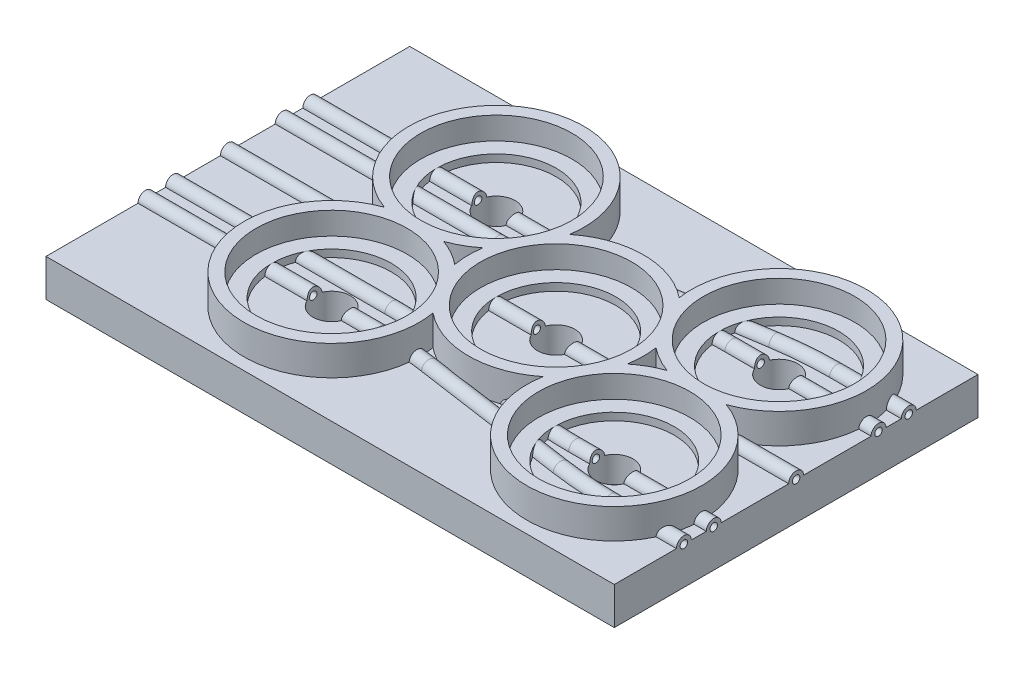
SolidWorks part; units mm, degrees
ref_plane "Front Plane" through (0, 0, 0) normal (0, 0, 1) x (1, 0, 0)
ref_plane "Top Plane" through (0, 0, 0) normal (0, 1, 0) x (1, 0, 0)
ref_plane "Right Plane" through (0, 0, 0) normal (1, 0, 0) x (0, 0, -1)
sketch "Sketch1" plane through (0, 0, 0) normal (0, 1, 0) x (1, 0, 0)
  line L1 (-42.9349, 26.7119) -> (33.1051, 26.7119)
  line L2 (-42.9349, 26.7119) -> (-42.9349, -21.9581)
  line L3 (-42.9349, -21.9581) -> (33.1051, -21.9581)
  line L4 (33.1051, 26.7119) -> (33.1051, -21.9581)
extrude "Boss-Extrude1" add sketch "Sketch1" along normal blind 5
sketch "Sketch2" plane through (0, 5, 0) normal (0, 1, 0) x (1, 0, 0)
  circle A0 centre (19.7951, 13.4019) radius 2.5
  circle A1 centre (19.7951, -8.6481) radius 2.5
  circle A2 centre (0.8851, 2.4819) radius 2.5
  circle A3 centre (-18.0249, 13.4019) radius 2.5
  circle A4 centre (-18.0249, -8.6481) radius 2.5
extrude "Cut-Extrude1" cut sketch "Sketch2" against normal blind 3.5
sketch "Sketch18" plane through (0, 5, 0) normal (0, 1, 0) x (1, 0, 0)
  circle A0 centre (0.8851, 2.4819) radius 2.5
  circle A1 centre (0.8851, 2.4819) radius 11.715
  circle A2 centre (-18.0249, 13.4019) radius 11.715
  circle A3 centre (-18.0249, 13.4019) radius 2.5
  circle A4 centre (19.7951, 13.4019) radius 2.5
  circle A5 centre (19.7951, 13.4019) radius 11.715
  circle A6 centre (19.7951, -8.6481) radius 2.5
  circle A7 centre (19.7951, -8.6481) radius 11.715
  circle A8 centre (-18.0249, -8.6481) radius 2.5
  circle A9 centre (-18.0249, -8.6481) radius 11.715
  circle A10 centre (0.8851, 2.4819) radius 8
  circle A11 centre (-18.0249, 13.4019) radius 8
  circle A12 centre (-18.0249, -8.6481) radius 8
  circle A13 centre (19.7951, -8.6481) radius 8
  circle A14 centre (19.7951, 13.4019) radius 8
extrude "Boss-Extrude6" add sketch "Sketch18" along normal blind 1 contours A9 A2 A1 A11 | A2 A9 | A1 A2 | A1 A9 A2 A12 | A1 A9 | A9 A1 A7 A5 A2 A10 | A1 A5 | A1 A7 | A7 A5 A1 A14 | A5 A7 | A5 A7 A1 A13 region at (12.2258, 5, -1.4944) region at (10.3401, 5, -7.9419) region at (11.3128, 5, -8.5036) region at (14.2083, 5, -1.2759) region at (10.3401, 5, 3.0831) region at (19.7951, 5, -2.3769) region at (-8.5699, 5, -7.9419) region at (-9.5426, 5, -8.5036) region at (-6.6794, 5, 7.6602) region at (-8.5699, 5, 3.0831) region at (-18.0249, 5, -2.3769)
sketch "Sketch21" plane through (0, 6, 0) normal (0, 1, 0) x (1, 0, 0)
  circle A0 centre (-18.0249, 13.4019) radius 11.715
  circle A1 centre (0.8851, 2.4819) radius 11.715
  circle A2 centre (19.7951, 13.4019) radius 11.715
  circle A3 centre (19.7951, -8.6481) radius 11.715
  circle A4 centre (-18.0249, -8.6481) radius 11.715
  circle A5 centre (-18.0249, 13.4019) radius 10.115
  circle A6 centre (0.8851, 2.4819) radius 10.115
  circle A7 centre (19.7951, -8.6481) radius 10.115
  circle A8 centre (-18.0249, -8.6481) radius 10.115
  circle A9 centre (19.7951, 13.4019) radius 10.115
  arc M3 (8.2564, -6.6234) -> (23.7562, 2.3769) centre (19.7951, -8.6481) ccw
  arc M4 (23.7562, 2.3769) -> (8.2165, 11.6192) centre (19.7951, 13.4019) ccw
  arc M5 (8.2165, 11.6192) -> (-6.4463, 11.6192) centre (0.8851, 2.4819) ccw
  arc M6 (-6.4463, 11.6192) -> (-21.9861, 2.3769) centre (-18.0249, 13.4019) ccw
  arc M8 (-6.4463, 11.6192) -> (-21.9861, 2.3769) centre (-18.0249, 13.4019) ccw
  arc M9 (-21.9861, 2.3769) -> (-6.4862, -6.6234) centre (-18.0249, -8.6481) ccw
  arc M11 (-21.9861, 2.3769) -> (-6.4862, -6.6234) centre (-18.0249, -8.6481) ccw
  arc M12 (-6.4862, -6.6234) -> (8.2564, -6.6234) centre (0.8851, 2.4819) ccw
  arc M13 (12.4637, 4.2645) -> (15.8339, 2.3769) centre (19.7951, 13.4019) ccw
  arc M14 (15.8339, 2.3769) -> (12.4238, 0.4571) centre (19.7951, -8.6481) ccw
  arc M15 (12.4238, 0.4571) -> (12.4637, 4.2645) centre (0.8851, 2.4819) ccw
  arc M17 (-10.6935, 4.2645) -> (-10.6536, 0.4571) centre (0.8851, 2.4819) ccw
  arc M18 (-10.6536, 0.4571) -> (-14.0638, 2.3769) centre (-18.0249, -8.6481) ccw
  arc M19 (-14.0638, 2.3769) -> (-10.6935, 4.2645) centre (-18.0249, 13.4019) ccw
extrude "Boss-Extrude7" add sketch "Sketch21" along normal blind 3 contours A4 A1 A5 M19 M6 M8 | A0 A4 | A1 A0 A8 M18 M9 M11 | A4 A3 A2 A0 A6 M12 M15 M5 M17 | A0 A1 | A1 A4 | A1 A2 | A1 A3 | A3 A1 A9 M4 M13 | A2 A1 A7 M14 M3 | A2 A3 region at (-6.6696, 6, -12.5328) region at (-18.0249, 6, -2.3769) region at (-18.0249, 6, -1.6542) region at (0.8851, 6, -13.8655) region at (-8.5699, 6, -7.9419) region at (18.9261, 6, -24.7571) region at (10.3401, 6, -7.9419) region at (-8.5699, 6, 3.0831) region at (10.3401, 6, 3.0831) region at (11.0093, 6, 3.477) region at (19.7951, 6, -2.3769)
sketch "Sketch26" plane through (-42.9349, 0, 0) normal (-1, 0, 0) x (0, 0, 1)
  line L0 (-26.7119, 5) -> (21.9581, 5) construction
  circle A0 centre (-2.3769, 5) radius 0.5
  circle A1 centre (-2.3769, 5) radius 1
sketch "Sketch27" plane through (0, 5, 0) normal (0, 1, 0) x (1, 0, 0)
  line L0 (-42.9349, 2.3769) -> (33.1051, 2.3769)
  line L1 (-42.9349, 3.3769) -> (-42.9349, 1.3769) construction
  line L2 (33.1051, -21.9581) -> (33.1051, 26.7119) construction
sweep "Sweep3" add profiles "Sketch26" path "Sketch27"
sketch "Sketch28" plane through (-42.9349, 0, 0) normal (-1, 0, 0) x (0, 0, 1)
  line L0 (-2.8769, 5) -> (-1.8769, 5) construction
  circle A0 centre (-2.3769, 5) radius 0.5
sweep "Cut-Sweep8" cut profiles "Sketch28" path "Sketch27<2>"
sketch "Sketch27<2>" plane through (0, 5, 0) normal (0, 1, 0) x (1, 0, 0) same geometry as "Sketch27"
sketch "Sketch31" plane through (-42.9349, 0, 0) normal (-1, 0, 0) x (0, 0, 1)
  line L1 (-1.3769, 5) -> (21.9581, 5) construction
  circle A0 centre (4.9581, 5) radius 0.5
  circle A1 centre (4.9581, 5) radius 1
sketch "Sketch32" plane through (0, 5, 0) normal (0, 1, 0) x (1, 0, 0)
  line L0 (-42.9349, -4.9581) -> (-13.6012, -4.9581)
  line L2 (-42.9349, -3.9581) -> (-42.9349, -5.9581) construction
  line L3 (-3.7115, -5.946) -> (4.7845, -7.6603)
  line L4 (14.6743, -8.6481) -> (33.1051, -8.6481)
  line L5 (33.1051, -21.9581) -> (33.1051, 1.3769) construction
  circle A0 centre (-18.0249, -8.6481) radius 10.115 construction
  circle A1 centre (19.7951, -8.6481) radius 10.115 construction
  circle A2 centre (19.7951, -8.6481) radius 10.115 construction
  arc A3 (4.7845, -7.6603) -> (14.6743, -8.6481) centre (14.6743, 41.3519) ccw
  arc A4 (-3.7115, -5.946) -> (-13.6012, -4.9581) centre (-13.6012, -54.9581) ccw
  point P17 (9.6801, -8.6481)
  point P20 (-8.607, -4.9581)
  dimension "D1" = 50
sweep "Sweep4" add profiles "Sketch31" path "Sketch32"
sketch "Sketch33" plane through (-42.9349, 0, 0) normal (-1, 0, 0) x (0, 0, 1)
  circle A0 centre (4.9581, 5) radius 0.5
sweep "Cut-Sweep9" cut profiles "Sketch33" path "Sketch32<2>"
sketch "Sketch32<2>" plane through (0, 5, 0) normal (0, 1, 0) x (1, 0, 0) same geometry as "Sketch32"
sketch "Sketch34" plane through (-42.9349, 0, 0) normal (-1, 0, 0) x (0, 0, 1)
  circle A0 centre (-9.7119, 5) radius 0.5
  circle A1 centre (-9.7119, 5) radius 1
sketch "Sketch36" plane through (0, 5, 0) normal (0, 1, 0) x (1, 0, 0)
  line L0 (-42.9349, 9.7119) -> (-14.0693, 9.7119)
  line L1 (-42.9349, 10.7119) -> (-42.9349, 8.7119) construction
  line L2 (-3.2736, 10.8912) -> (2.7467, 12.2225)
  line L3 (13.5423, 13.4019) -> (33.1051, 13.4019)
  line L4 (33.1051, 3.3769) -> (33.1051, 26.7119) construction
  circle A0 centre (-18.0249, 13.4019) radius 10.115 construction
  arc A1 (25.8565, 3.3769) -> (8.2165, 11.6192) centre (19.7951, 13.4019) ccw construction
  arc A2 (23.7562, 2.3769) -> (8.2165, 11.6192) centre (19.7951, 13.4019) ccw construction
  arc A3 (2.7467, 12.2225) -> (13.5423, 13.4019) centre (13.5423, -36.5981) cw
  arc A4 (-3.2736, 10.8912) -> (-14.0693, 9.7119) centre (-14.0693, 59.7119) cw
  point P19 (8.0801, 13.4019)
  point P22 (-8.607, 9.7119)
  dimension "D1" = 50
sweep "Sweep5" add profiles "Sketch34" path "Sketch36"
sketch "Sketch37" plane through (-42.9349, 0, 0) normal (-1, 0, 0) x (0, 0, 1)
  line L0 (-10.2119, 5) -> (-9.2119, 5) construction
  circle A0 centre (-9.7119, 5) radius 0.5
sweep "Cut-Sweep10" cut profiles "Sketch37" path "Sketch36<2>"
sketch "Sketch36<2>" plane through (0, 5, 0) normal (0, 1, 0) x (1, 0, 0) same geometry as "Sketch36"
sketch "Sketch38" plane through (-42.9349, 0, 0) normal (-1, 0, 0) x (0, 0, 1)
  line L1 (5.9581, 5) -> (21.9581, 5) construction
  circle A0 centre (8.6481, 5) radius 0.5
  circle A1 centre (8.6481, 5) radius 1
sketch "Sketch39" plane through (0, 5, 0) normal (0, 1, 0) x (1, 0, 0)
  line L0 (-42.9349, -8.6481) -> (-11.5008, -8.6481)
  line L1 (-42.9349, -7.6481) -> (-42.9349, -9.6481) construction
  line L3 (-4.3559, -9.1613) -> (16.2411, -12.135)
  line L4 (23.3859, -12.6481) -> (33.1051, -12.6481)
  line L5 (33.1051, -21.9581) -> (33.1051, -9.6481) construction
  circle A0 centre (-18.0249, -8.6481) radius 10.115 construction
  arc A2 (16.2411, -12.135) -> (23.3859, -12.6481) centre (23.3859, 37.3519) ccw
  arc A3 (-4.3559, -9.1613) -> (-11.5008, -8.6481) centre (-11.5008, -58.6481) ccw
  point P13 (-7.9099, -8.6481)
  dimension "D1" = 50
sweep "Sweep6" add profiles "Sketch38" path "Sketch39"
sketch "Sketch40" plane through (-42.9349, 0, 0) normal (-1, 0, 0) x (0, 0, 1)
  line L0 (8.1481, 5) -> (9.1481, 5) construction
  circle A0 centre (8.6481, 5) radius 0.5
sweep "Cut-Sweep11" cut profiles "Sketch40" path "Sketch39<2>"
sketch "Sketch39<2>" plane through (0, 5, 0) normal (0, 1, 0) x (1, 0, 0) same geometry as "Sketch39"
sketch "Sketch41" plane through (-42.9349, 0, 0) normal (-1, 0, 0) x (0, 0, 1)
  line L1 (-26.7119, 5) -> (-10.7119, 5) construction
  circle A0 centre (-13.4019, 5) radius 0.5
  circle A1 centre (-13.4019, 5) radius 1
sketch "Sketch42" plane through (0, 5, 0) normal (0, 1, 0) x (1, 0, 0)
  line L0 (-42.9349, 13.4019) -> (-10.1825, 13.4019)
  line L1 (-42.9349, 13.9019) -> (-42.9349, 12.9019) construction
  line L3 (-2.4835, 13.9982) -> (15.8008, 16.8476)
  line L4 (23.4998, 17.4439) -> (33.1051, 17.4439)
  line L5 (33.1051, 14.4019) -> (33.1051, 26.7119) construction
  arc A0 (-6.4463, 11.6192) -> (-21.9861, 2.3769) centre (-18.0249, 13.4019) ccw construction
  arc A1 (15.8008, 16.8476) -> (23.4998, 17.4439) centre (23.4998, -32.5561) cw
  arc A2 (-2.4835, 13.9982) -> (-10.1825, 13.4019) centre (-10.1825, 63.4019) cw
  point P10 (0, 0)
  point P17 (-6.3099, 13.4019)
  dimension "D1" = 50
sweep "Sweep7" add profiles "Sketch41" path "Sketch42"
sketch "Sketch43" plane through (-42.9349, 0, 0) normal (-1, 0, 0) x (0, 0, 1)
  line L0 (-12.9019, 5) -> (-13.9019, 5) construction
  circle A0 centre (-13.4019, 5) radius 0.5
sweep "Cut-Sweep12" cut profiles "Sketch43" path "Sketch42<2>"
sketch "Sketch42<2>" plane through (0, 5, 0) normal (0, 1, 0) x (1, 0, 0) same geometry as "Sketch42"
sketch "Sketch44" plane through (0, 1.5, 0) normal (0, 1, 0) x (1, 0, 0)
  circle A0 centre (-18.0249, 13.4019) radius 2.5
  circle A1 centre (-18.0249, -8.6481) radius 2.5
  circle A2 centre (19.7951, -8.6481) radius 2.5
  circle A3 centre (0.8851, 2.4819) radius 2.5
  circle A4 centre (19.7951, 13.4019) radius 2.5
extrude "Cut-Extrude5" cut sketch "Sketch44" along normal blind 23
